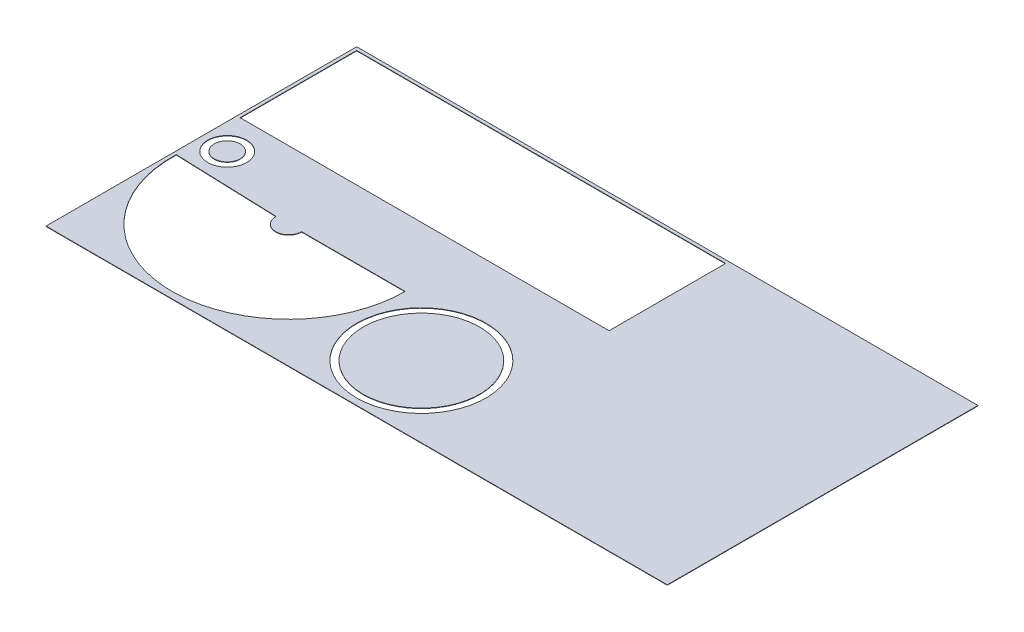
SolidWorks part; units mm, degrees
ref_plane "Front Plane" through (0, 0, 0) normal (0, 0, 1) x (1, 0, 0)
ref_plane "Top Plane" through (0, 0, 0) normal (0, 1, 0) x (1, 0, 0)
ref_plane "Right Plane" through (0, 0, 0) normal (1, 0, 0) x (0, 0, -1)
sketch "Sketch1" plane through (0, 0, 0) normal (0, 1, 0) x (1, 0, 0)
  line L1 (-1219.2, -609.6) -> (1219.2, -609.6)
  line L2 (-1219.2, -609.6) -> (-1219.2, 609.6)
  line L3 (-1219.2, 609.6) -> (1219.2, 609.6)
  line L4 (1219.2, -609.6) -> (1219.2, 609.6)
  line L5 (-1219.2, -609.6) -> (1219.2, 609.6) construction
  line L6 (-1219.2, 609.6) -> (1219.2, -609.6) construction
  point P0 (0, 0)
  dimension "D1" = 1219.2
  dimension "D2" = 2438.4
base flange "Base-Flange1" sketch "Sketch1" thickness 1.5875 reverse thickness direction no parameters "D1"=0.7366
sketch "Sketch6" plane through (0, 0, 0) normal (0, 1, 0) x (1, 0, 0)
  line L0 (1219.2, 609.6) -> (-1219.2, 609.6) construction
  line L1 (-1206.5, 596.9) -> (241.3, 596.9)
  line L2 (-1206.5, 596.9) -> (-1206.5, 139.7)
  line L3 (-1206.5, 139.7) -> (241.3, 139.7)
  line L4 (241.3, 596.9) -> (241.3, 139.7)
  line L5 (-1219.2, 609.6) -> (-1219.2, -609.6) construction
  line L6 (-698.7785, -127) -> (-292.3785, -127)
  line L7 (-1206.5, -111.044) -> (-800.3476, -125.2271)
  line L9 (-1219.2, -609.6) -> (1219.2, -609.6) construction
  arc A0 (-292.3785, -127) -> (-1206.5, -111.044) centre (-749.5785, -127) cw
  arc A1 (-800.3476, -125.2271) -> (-698.7785, -127) centre (-749.5785, -127) ccw
  circle A2 centre (-25.4, -330.2) radius 228.6
  circle A3 centre (-25.4, -330.2) radius 254
  circle A4 centre (-1117.6, 0) radius 50.8
  circle A5 centre (-1117.6, 0) radius 76.2
  dimension "D5" = 457.2
  dimension "D10" = 457.2
  dimension "D11" = 508
  dimension "D12" = 101.6
  dimension "D13" = 152.4
  dimension "D1" = 457.2
  dimension "D2" = 1447.8
  dimension "D3" = 12.7
  dimension "D4" = 12.7
  dimension "D6" = 406.4
  dimension "D7" = 182
  dimension "D8" = 12.7
  dimension "D9" = 482.6
  dimension "D14" = 101.6
  dimension "D15" = 279.4
  dimension "D16" = 1193.8
  dimension "D17" = 609.6
extrude "Cut-Extrude3" cut sketch "Sketch6" against normal through all normal cut yes
sketch "Bend-Lines1" plane through (0, 0, 0) normal (0, 1, 0) x (1, 0, 0)
sketch "Bounding-Box1" plane through (0, 0, 0) normal (0, 1, 0) x (1, 0, 0)
sheet metal parameters "Sheet-Metal(1)" thickness 1.5875 parameters "D1"=0.7366
flat pattern "Flat-Pattern(1)" [suppressed]
sketch "Bend-Lines2" plane through (0, 0, 0) normal (0, 1, 0) x (1, 0, 0)
sketch "Bounding-Box2" [suppressed] plane through (0, 0, 0) normal (0, 1, 0) x (1, 0, 0)
sheet metal parameters "Sheet-Metal(6)" thickness 1.5875 parameters "D1"=0.7366
flat pattern "Flat-Pattern(6)"
sketch "Bend-Lines6" plane through (0, 0, 0) normal (0, 1, 0) x (1, 0, 0)
sketch "Bounding-Box6" [suppressed] plane through (0, 0, 0) normal (0, 1, 0) x (1, 0, 0)
sheet metal parameters "Sheet-Metal(7)" thickness 1.5875 parameters "D1"=0.7366
flat pattern "Flat-Pattern(7)"
sketch "Bend-Lines7" plane through (0, 0, 0) normal (0, 1, 0) x (1, 0, 0)
sketch "Bounding-Box7" [suppressed] plane through (0, 0, 0) normal (0, 1, 0) x (1, 0, 0)
sheet metal parameters "Sheet-Metal(8)" thickness 1.5875 parameters "D1"=0.7366
flat pattern "Flat-Pattern(8)"
sketch "Bend-Lines8" plane through (0, 0, 0) normal (0, 1, 0) x (1, 0, 0)
sketch "Bounding-Box8" [suppressed] plane through (0, 0, 0) normal (0, 1, 0) x (1, 0, 0)
